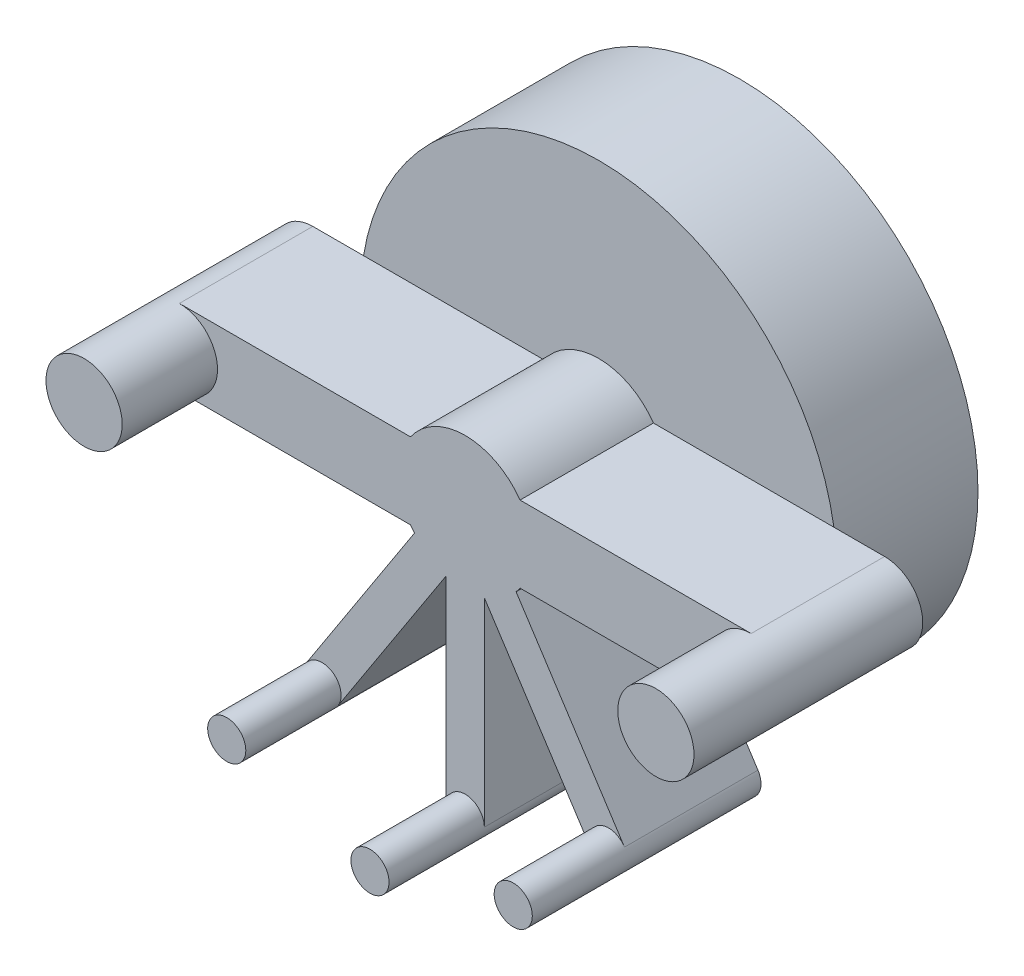
SolidWorks part; units mm, degrees
ref_plane "Front Plane" through (0, 0, 0) normal (0, 0, 1) x (1, 0, 0)
ref_plane "Top Plane" through (0, 0, 0) normal (0, 1, 0) x (1, 0, 0)
ref_plane "Right Plane" through (0, 0, 0) normal (1, 0, 0) x (0, 0, -1)
sketch "main_features_sketch" plane through (0, 0, 0) normal (0, 0, 1) x (1, 0, 0)
  line L0 (-7.5, 0) -> (7.5, 0) construction
  line L1 (0, 0) -> (0, -6.9) construction
  line L2 (0, 0) -> (3.758, -5.7868) construction
  line L3 (0, 0) -> (-3.758, -5.7868) construction
  line L4 (-7.5, -1) -> (7.5, -1)
  line L5 (7.5, 1) -> (-7.5, 1)
  line L6 (-4.1773, -5.5145) -> (-1.3327, -1.1342)
  line L7 (-3.3387, -6.0591) -> (-0.4941, -1.6788)
  line L8 (-0.5, -6.9) -> (-0.5, -1.6771)
  line L9 (0.5, -6.9) -> (0.5, -1.6771)
  line L10 (3.3387, -6.0591) -> (0.4941, -1.6788)
  line L11 (4.1773, -5.5145) -> (1.3327, -1.1342)
  circle A0 centre (0, 0) radius 6.25
  circle A1 centre (0, 0) radius 1.75
  circle A2 centre (-7.5, 0) radius 1
  circle A3 centre (7.5, 0) radius 1
  circle A4 centre (3.758, -5.7868) radius 0.5
  circle A5 centre (0, -6.9) radius 0.5
  circle A6 centre (-3.758, -5.7868) radius 0.5
  point P7 (0, 0)
  point P29 (0.7977, -1.5576)
  point P30 (0, 0)
  dimension "D1" = 3.5
  dimension "D2" = 12.5
  dimension "D3" = 2
  dimension "D5" = 1
  dimension "D4" = 15
  dimension "D6" = 6.9
  dimension "D7" = 33
extrude "support" add sketch "main_features_sketch" along normal blind 3.5 contours A2 | A2 L4 A0 L5 | A1 L5 A0 L4 | A1 L4 A0 L5 | A3 L5 A0 L4 | A3 | A1 L9 L10 A0 L11 | A4 L11 A0 L10 | A4 | A5 | A5 L9 A0 L8 | A1 L7 L8 A0 L9 L10 | A6 | A6 L7 A0 L6 | A1 L6 A0 L7 L8 | A1 L8 L7 | A1 L10 L9 | A1 region at (-6.7759, -0.7241, 0) region at (-7.5, 0, 0) region at (-3.9355, 0, 0) region at (-3.4851, -5.3665, 0) region at (-2.1702, -3.3417, 0) region at (3.9355, 0, 0) region at (6.8347, 0.976, 0) region at (-3.758, -5.7868, 0) region at (2.1702, -3.3417, 0) region at (-0.498, -1.6813, 0) region at (7.5, 0, 0) region at (0, -3.9846, 0) region at (0, -6.3988, 0) region at (3.4851, -5.3665, 0) region at (0.498, -1.6813, 0) region at (0, -6.9, 0) region at (3.758, -5.7868, 0)
extrude "knob" add sketch "main_features_sketch<3>" against normal blind 3.7 contours A0
sketch "main_features_sketch<3>" plane through (0, 0, 0) normal (0, 0, 1) x (1, 0, 0) same geometry as "main_features_sketch"
extrude "shaft" add sketch "main_features_sketch<4>" against normal blind 0.9 from surface contours A1 starting at face at (6.25, 0, -3.7)
sketch "main_features_sketch<4>" plane through (0, 0, 0) normal (0, 0, 1) x (1, 0, 0) same geometry as "main_features_sketch"
extrude "legs" add sketch "main_features_sketch<5>" along normal blind 2.5 from surface contours A2 | A6 | A5 | A4 | A3 region at (-7.5, 0, 0) region at (-3.758, -5.7868, 0) region at (7.5, 0, 0) region at (0, -6.9, 0) region at (3.758, -5.7868, 0) starting at face at (0, -2.399, 3.5)
sketch "main_features_sketch<5>" plane through (0, 0, 0) normal (0, 0, 1) x (1, 0, 0) same geometry as "main_features_sketch"
